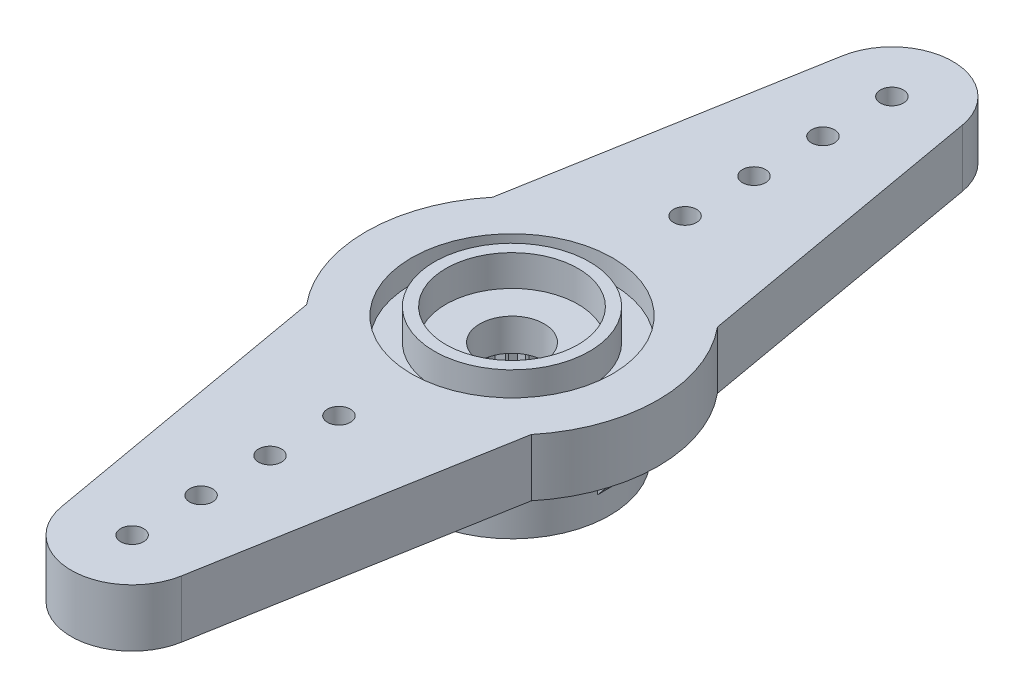
SolidWorks part; units mm, degrees
material "PC High Viscosity"
ref_plane "Front Plane" through (0, 0, 0) normal (0, 0, 1) x (1, 0, 0)
ref_plane "Top Plane" through (0, 0, 0) normal (0, 1, 0) x (1, 0, 0)
ref_plane "Right Plane" through (0, 0, 0) normal (1, 0, 0) x (0, 0, -1)
sketch "BaseS" plane through (0, 0, 0) normal (0, 1, 0) x (1, 0, 0)
  circle A0 centre (0, 0) radius 6.35
  dimension "D1" = 12.7
extrude "BASE" add sketch "BaseS" along normal blind 5.4
sketch "TopBoreS" plane through (0, 5.4, 0) normal (0, 1, 0) x (1, 0, 0)
  circle A0 centre (0, 0) radius 1.4
  dimension "D1" = 2.8
extrude "TOP BORE" cut sketch "TopBoreS" against normal through all
sketch "HornHalfS" plane through (0, 5.4, 0) normal (0, 1, 0) x (1, 0, 0)
  line L0 (0, 0) -> (0, 16.53) construction
  line L1 (-2.6097, 16.9902) -> (-4.8916, 4.049)
  line L2 (0, 19.18) -> (0, 16.53) construction
  line L3 (2.6097, 16.9902) -> (4.8916, 4.049)
  arc A0 (2.6097, 16.9902) -> (-2.6097, 16.9902) centre (0, 16.53) ccw
  arc A1 (4.8916, 4.049) -> (-4.8916, 4.049) centre (0, 0) ccw
  circle A2 centre (0, 0) radius 6.35 construction
  dimension "D1" = 5.3
  dimension "D2" = 19.18
  dimension "D3" = 10
  dimension "D4" = 9.7832
extrude "HORN HALF" add sketch "HornHalfS" against normal blind 2.5
sketch "HornAttachS" plane through (0, 5.4, 0) normal (0, 1, 0) x (1, 0, 0)
  circle A0 centre (0, 16.53) radius 0.5
  dimension "D1" = 1
extrude "HORN ATTACH" cut sketch "HornAttachS" against normal through all
sketch "HA LP RS" plane through (0, 0, 0) normal (0, 1, 0) x (1, 0, 0)
  line L0 (0, 0) -> (0, 16.53) construction
pattern_linear "HA LP" count 4 spacing 3 along (0, 0, 1) of "HORN ATTACH"
mirror "HORN BODIES" about plane through (0, 0, 0) normal (0, 0, 1) of "HA LP", "HORN ATTACH", "HORN HALF"
sketch "ToothS" plane through (0, 0, 0) normal (0, -1, 0) x (1, 0, 0)
  line L0 (0, -2.9) -> (0.2629, -2.5867)
  line L1 (0, -2.9) -> (-0.2629, -2.5867)
  line L2 (0, -2.6) -> (0, -2.9) construction
  line L3 (0, 0) -> (0, -2.6) construction
  arc A0 (-0.2629, -2.5867) -> (0.2629, -2.5867) centre (0, 0) ccw
  dimension "D1" = 5.2
  dimension "D2" = 80
  dimension "D3" = 0.3
extrude "TOOTH" cut sketch "ToothS" against normal blind 3
pattern_circular "TOOTH CP" count 26 over 360 about axis through (0, 5.4, 0) along (0, -1, 0) of "TOOTH"
sketch "BottomBoreS" plane through (0, 0, 0) normal (0, -1, 0) x (-1, 0, 0)
  circle A0 centre (0, 0) radius 2.6
  arc A1 (0.2629, 2.5867) -> (-0.2629, 2.5867) centre (0, 0) ccw construction
extrude "BOTTOM BORE" cut sketch "BottomBoreS" against normal up to surface (3 mm away) up to face at (-0.6451, 3, 2.6172)
sketch "HoldingShaftS" plane through (0, 0, 0) normal (0, -1, 0) x (1, 0, 0)
  circle A0 centre (0, 0) radius 6.35 construction
  circle A1 centre (0, 0) radius 6.35
  circle A2 centre (0, 0) radius 4.25
  dimension "D1" = 2.1
  dimension "D2" = 8.5
extrude "HOLDING SHAFT" cut sketch "HoldingShaftS" against normal up to surface (2.9 mm away) up to face at (0, 2.9, -13.03)
sketch "RibS" plane through (0, 0, 0) normal (0, 0, 1) x (1, 0, 0)
  line L0 (4.21, 1) -> (5.8043, 2.9)
  line L1 (5.8043, 2.9) -> (4.21, 2.9)
  line L2 (4.21, 1) -> (4.16, 1)
  line L3 (4.16, 1) -> (4.16, 2.9)
  line L4 (4.21, 1) -> (4.21, 2.9) construction
  line L5 (4.16, 2.9) -> (4.21, 2.9)
  line L6 (-4.25, 2.9) -> (4.25, 2.9) construction
  line L7 (4.21, 2.9) -> (4.25, 2.9) construction
  line L8 (4.25, 0) -> (4.25, 2.9) construction
  dimension "D1" = 1.9
  dimension "D2" = 0.05
  dimension "D3" = 40
  dimension "D4" = 0.09
extrude "RIB" add sketch "RibS" along normal mid plane 1
pattern_circular "RIB CP" count 4 over 360 about axis through (0, 20.8605, 0) along (0, -1, 0) of "RIB"
sketch "TopCutS" plane through (0, 5.4, 0) normal (0, 1, 0) x (1, 0, 0)
  circle A0 centre (0, 0) radius 4.375
  arc A1 (4.8916, -4.049) -> (4.8916, 4.049) centre (0, 0) ccw construction
  dimension "D1" = 1.975
  dimension "D2" = 8.75
extrude "TOP CUT" cut sketch "TopCutS" against normal blind 1
sketch "TopPocketCylinderS" plane through (0, 4.4, 0) normal (0, 1, 0) x (1, 0, 0)
  circle A0 centre (0, 0) radius 2.875
  circle A1 centre (0, 0) radius 3.375
  circle A2 centre (0, 0) radius 4.375 construction
  dimension "D2" = 0.5
  dimension "D1" = 1
  dimension "D3" = 6.75
extrude "TOP POCKET CYLINDER" add sketch "TopPocketCylinderS" along normal offset from surface (1.35 mm away) 0.35 up to face at (0, 5.4, 4.375) offset beyond the face yes
